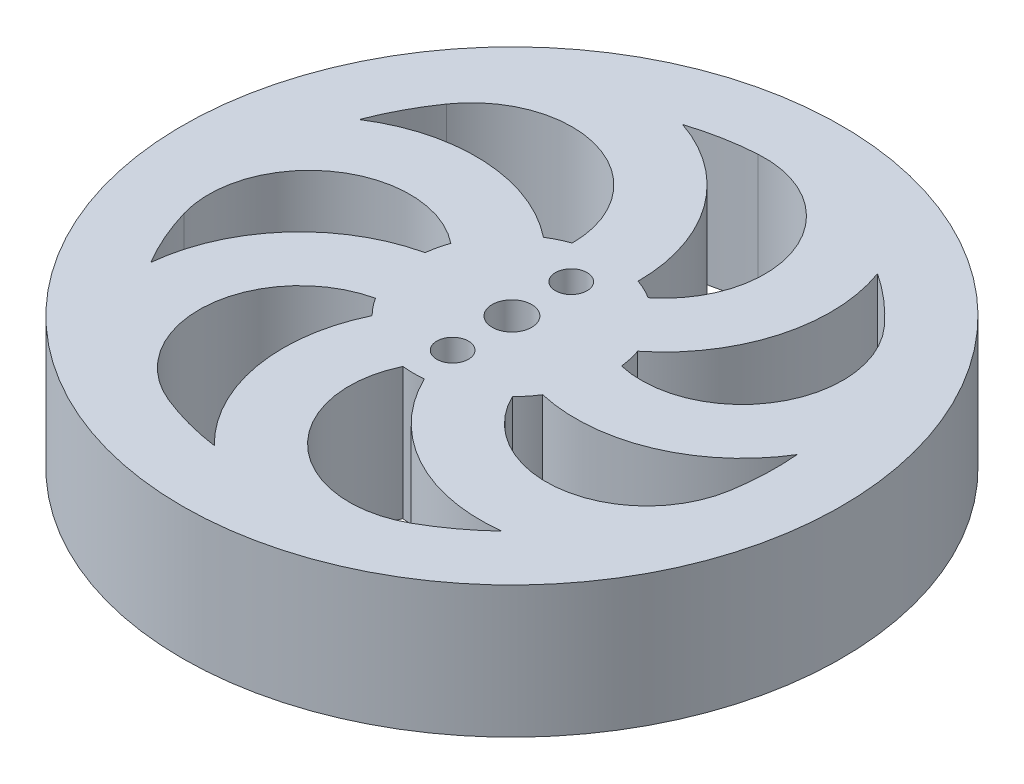
SolidWorks part; units mm, degrees
material "Rubber"
ref_plane "Front Plane" through (0, 0, 0) normal (0, 0, 1) x (1, 0, 0)
ref_plane "Top Plane" through (0, 0, 0) normal (0, 1, 0) x (1, 0, 0)
ref_plane "Right Plane" through (0, 0, 0) normal (1, 0, 0) x (0, 0, -1)
sketch "Base Reference Sketch" plane through (0, 0, 0) normal (0, 1, 0) x (1, 0, 0)
  line L0 (-2.5, 7.0711) -> (2.5, 7.0711) construction
  line L1 (0, 7.5) -> (0, 1.5) construction
  circle A0 centre (0, 0) radius 25
  circle A1 centre (0, 0) radius 20
  circle A2 centre (0, 0) radius 1.5
  circle A3 centre (0, 0) radius 7.5
  arc A4 (-2.5, 7.0711) -> (-16.4045, 11.4408) centre (-10.1389, 7.0711) ccw
  arc A5 (2.5, 7.0711) -> (-6.0997, 19.0471) centre (-10.1389, 7.0711) ccw
  arc A6 (2.5, 7.0711) -> (-20.5056, 14.301) centre (-10.1389, 7.0711) ccw construction
  circle A7 centre (0, 0) radius 7.5 construction
  point P14 (0, 4.5)
  point P15 (0, 3.5)
  dimension "D1" = 50
  dimension "D3" = 6
  dimension "D2" = 5
  dimension "D4" = 3
  dimension "D5" = 5
  dimension "D6" = 0
extrude "Base Wheel Extrude" add sketch "Base Reference Sketch" along normal blind 10 contours A0 A1 | A3 A5 A1 A4 | A3 A2 region at (-24.2929, 0, 0) region at (-3.9604, 0, -13.5673) region at (5.9505, 0, -4.2077)
pattern_circular "Spokes Circular Pattern" count 7 over 360 about axis through (0, 10, 0) along (0, -1, 0) of "Base Wheel Extrude"
hole_wizard "M2 Clearance Hole1" positions "Sketch1" profile "Sketch2" hole size "M2" standard "ISO" end condition through all
sketch "Sketch1" plane through (0, 0, 0) normal (0, -1, 0) x (-1, 0, 0)
  point P0 (0, 4.5)
sketch "Sketch2" plane through (0, 0, -4.5) normal (1, 0, 0) x (0, 0, -1)
  line L0 (0, 0) -> (0, 10)
  line L1 (0, 10) -> (1.2, 10)
  line L2 (1.2, 10) -> (1.2, 0)
  line L5 (1.2, 0) -> (0, 0)
  line L11 (0, -6.35) -> (0, 107.95) construction
  dimension "Thru Hole Dia." = 2.4
  dimension "Thru Hole Depth" = 10
pattern_circular "CirPattern1" count 2 over 360 about axis through (0, 10, 0) along (0, -1, 0) of "M2 Clearance Hole1" reverse direction yes
equation "\"wheeldia\"= 50mm"
equation "\"wheelthick\"= 3mm"
equation "\"wheelwide\"= 10mm"
equation "\"wheelspokes\"= 7"
